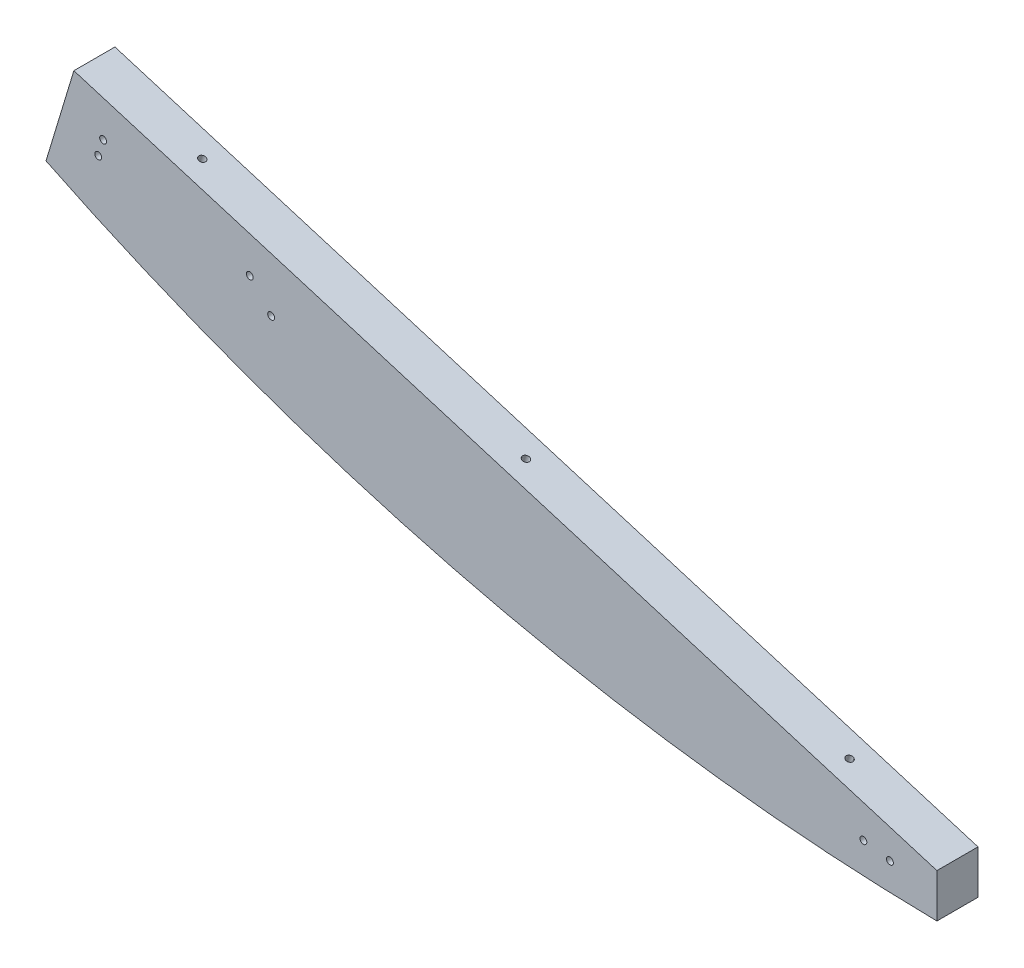
SolidWorks part; units mm, degrees
material "Beech"
ref_plane "Front Plane" through (0, 0, 0) normal (0, 0, 1) x (1, 0, 0)
ref_plane "Top Plane" through (0, 0, 0) normal (0, 1, 0) x (1, 0, 0)
ref_plane "Right Plane" through (0, 0, 0) normal (1, 0, 0) x (0, 0, -1)
sketch "Sketch1" plane through (0, 0, 0) normal (0, 0, 1) x (1, 0, 0)
  line L0 (-400.1409, 384.3517) -> (0, 263.2469)
  line L1 (134.7, 222.4793) -> (-400.1409, 384.3517) construction
  line L2 (0, 263.2469) -> (0, 242.9943)
  line L3 (-413.0591, 341.6688) -> (-426.0964, 298.5925) construction
  line L4 (0, -223.9129) -> (0, 250.6666) construction
  line L5 (-400.1409, 384.3517) -> (-396.462, 396.5071) construction
  line L9 (-400.1409, 384.3517) -> (-413.0591, 341.6688)
  line L10 (0, 242.9943) -> (0, 198.54) construction
  arc A0 (-413.0591, 341.6688) -> (0, 242.9943) centre (13.752, 1214.4469) ccw
  arc A1 (-406.853, 338.6611) -> (0.6017, 242.9859) centre (13.752, 1214.4469) ccw construction
  arc A2 (-426.0964, 298.5925) -> (0, 198.54) centre (13.752, 1214.4469) ccw construction
  dimension "D1" = 1016
  dimension "D4" = 971.55
  dimension "D2" = 914.4
  dimension "D3" = 1214.4469
  dimension "D5" = 20.2527
extrude "Boss-Extrude1" add sketch "Sketch1" against normal blind 19.05
ref_plane "CL" through (0, 0, -9.525) normal (0, 0, 1) x (1, 0, 0)
hole_wizard "Hole1" positions "Sketch2" profile "Sketch3" legacy
sketch "Sketch2" plane through (390.3751, 158.3668, -217.3) normal (0.2897, 0.9571, 0) x (0, 0, -1)
  line L4 (-207.775, 822.0847) -> (-207.775, 404.0189) construction
  line L8 (-207.775, 822.0847) -> (-207.775, 717.5683)
  line L9 (-207.775, 717.5683) -> (-207.775, 613.0518)
  line L10 (-207.775, 613.0518) -> (-207.775, 508.5353)
  line L11 (-207.775, 508.5353) -> (-207.775, 404.0189)
  line L12 (-108.65, 822.0847) -> (-108.65, 404.0189) construction
  line L15 (0, 822.0847) -> (0, 613.0518) construction
  line L18 (-207.775, 388.2192) -> (-207.775, 263.2847) construction
  line L22 (-207.775, 388.2192) -> (-207.775, 356.9856)
  line L23 (-207.775, 356.9856) -> (-207.775, 325.752)
  line L24 (-207.775, 325.752) -> (-207.775, 294.5183)
  line L25 (-207.775, 294.5183) -> (-207.775, 263.2847)
  line L26 (0, 388.2192) -> (0, 263.2847) construction
  line L30 (0, 263.2847) -> (0, 294.5183)
  line L31 (0, 294.5183) -> (0, 325.752)
  line L32 (0, 325.752) -> (0, 356.9856)
  line L33 (0, 356.9856) -> (0, 388.2192)
  point P24 (-207.775, 613.0518)
  point P31 (-207.775, 456.2771)
  point P33 (-207.775, 769.8265)
  point P52 (-108.65, 456.2771)
  point P54 (-108.65, 630.1265)
  point P56 (-108.65, 769.8265)
  point P76 (-207.775, 356.9856)
  point P80 (-207.775, 294.5183)
  point P99 (0, 294.5183)
  point P104 (0, 356.9856)
  point P113 (207.775, 294.5183)
  point P114 (207.775, 356.9856)
  point P115 (108.65, 769.8265)
  point P116 (108.65, 630.1265)
  point P117 (108.65, 456.2771)
  point P118 (207.775, 769.8265)
  point P119 (207.775, 456.2771)
  point P120 (207.775, 613.0518)
  dimension "D1" = 139.7
sketch "Sketch3" plane through (-196.3915, 335.9548, -425.075) normal (0, 0, 1) x (-0.9571, 0.2897, 0)
  line L0 (0, 0) -> (0, 32.7039)
  line L1 (0, 32.7039) -> (1.5875, 31.75)
  line L2 (1.5875, 31.75) -> (1.5875, 4.0177)
  line L3 (1.5875, 4.0177) -> (5.08, 0)
  line L4 (5.08, 0) -> (0, 0)
  line L5 (0, -14.3089) -> (0, 102.4216) construction
  line L6 (0, 32.7039) -> (-1.5875, 31.75) construction
  line L7 (-1.5875, 4.0177) -> (-5.08, 0) construction
  dimension "Diameter" = 3.175
  dimension "Depth" = 31.75
  dimension "C-Sink Diameter" = 10.16
  dimension "C-Sink Angle" = 82
  dimension "Drill Angle" = 118
hole_wizard "Hole2" positions "Sketch4" profile "Sketch5" legacy
sketch "Sketch4" plane through (277.2867, -215.2871, 12.7) normal (0, 0, 1) x (-0.09, 0.9959, 0)
  line L0 (54.6742, 260.7254) -> (44.8416, 151.8686) construction
  line L6 (458.2175, 188.8136) -> (426.7882, 117.3689) construction
  line L11 (486.0396, 272.5028) -> (513.4071, 262.4897) construction
  line L19 (643.2075, 626.7743) -> (602.3132, 525.5573) construction
  line L24 (664.0363, 618.3589) -> (454.7061, 100.2486) construction
  line L28 (664.0363, 618.3589) -> (611.7037, 488.8313)
  line L29 (611.7037, 488.8313) -> (559.3712, 359.3037)
  line L30 (559.3712, 359.3037) -> (507.0387, 229.7761)
  line L31 (507.0387, 229.7761) -> (454.7061, 100.2486)
  line L33 (513.4071, 262.4897) -> (486.0396, 272.5028)
  point P12 (52.9605, 241.7526)
  point P14 (47.6978, 183.4898)
  point P29 (434.4591, 134.8062)
  point P31 (453.1036, 177.1887)
  point P48 (499.7233, 267.4963)
  point P79 (636.0712, 609.1114)
  point P81 (609.4494, 543.2202)
  point P98 (559.3712, 359.3037)
  point P100 (507.0387, 229.7761)
  point P112 (637.87, 553.5951)
  dimension "D1" = 19.05
  dimension "D2" = 31.75
  dimension "D3" = 12.7
  dimension "D4" = 19.05
  dimension "D5" = 19.05
  dimension "D6" = 19.05
sketch "Sketch5" plane through (-331.4463, 370.1954, 12.7) normal (1, 0, 0) x (0, -1, 0)
  line L0 (0, 0) -> (0, 32.7039)
  line L1 (0, 32.7039) -> (1.5875, 31.75)
  line L2 (1.5875, 31.75) -> (1.5875, 4.0177)
  line L3 (1.5875, 4.0177) -> (5.08, 0)
  line L4 (5.08, 0) -> (0, 0)
  line L5 (0, -14.3089) -> (0, 102.4216) construction
  line L6 (0, 32.7039) -> (-1.5875, 31.75) construction
  line L7 (-1.5875, 4.0177) -> (-5.08, 0) construction
  dimension "Diameter" = 3.175
  dimension "Depth" = 31.75
  dimension "C-Sink Diameter" = 10.16
  dimension "C-Sink Angle" = 82
  dimension "Drill Angle" = 118
hole_wizard "Hole3" positions "Sketch6" profile "Sketch7" legacy
sketch "Sketch6" plane through (277.2867, -215.2871, -31.75) normal (0, 0, -1) x (0.09, -0.9959, 0)
  point P4 (-507.0387, 229.7761)
  point P6 (-559.3712, 359.3037)
  point P8 (-637.87, 553.5951)
  point P10 (-628.7751, 612.0592)
  point P12 (-597.3958, 534.3927)
  point P16 (-496.527, 255.4282)
  point P18 (-441.05, 168.3613)
  point P20 (-426.601, 135.516)
  point P22 (-41.7953, 242.7611)
  point P24 (-36.5327, 184.4983)
sketch "Sketch7" plane through (2.8292, 269.0251, -31.75) normal (1, 0, 0) x (0, 1, 0)
  line L0 (0, 0) -> (0, 32.7039)
  line L1 (0, 32.7039) -> (1.5875, 31.75)
  line L2 (1.5875, 31.75) -> (1.5875, 4.0177)
  line L3 (1.5875, 4.0177) -> (5.08, 0)
  line L4 (5.08, 0) -> (0, 0)
  line L5 (0, -14.3089) -> (0, 102.4216) construction
  line L6 (0, 32.7039) -> (-1.5875, 31.75) construction
  line L7 (-1.5875, 4.0177) -> (-5.08, 0) construction
  dimension "Diameter" = 3.175
  dimension "Depth" = 31.75
  dimension "C-Sink Diameter" = 10.16
  dimension "C-Sink Angle" = 82
  dimension "Drill Angle" = 118
hole_wizard "Hole4" positions "Sketch8" profile "Sketch9" legacy
sketch "Sketch8" plane through (-521.7058, 26.5321, -217.3) normal (-0.9571, 0.2897, 0) x (0, 0, 1)
  line L0 (207.775, 377.6924) -> (207.775, 333.0975) construction
  line L4 (108.65, 377.6924) -> (108.65, 333.0975) construction
  line L8 (175, 506.2803) -> (175, 390.3924) construction
  line L12 (94.25, 390.3924) -> (94.25, 377.6924) construction
  line L17 (94.25, 384.0424) -> (217.3, 384.0424) construction
  line L19 (94.25, 384.0424) -> (135.2667, 384.0424)
  line L20 (135.2667, 384.0424) -> (176.2833, 384.0424)
  line L21 (176.2833, 384.0424) -> (217.3, 384.0424)
  line L22 (0, 333.0975) -> (0, 390.3924) construction
  point P39 (108.65, 355.3949)
  point P41 (207.775, 355.3949)
  point P43 (175, 448.3363)
  point P47 (135.2667, 384.0424)
  point P49 (176.2833, 384.0424)
  point P65 (-175, 448.3363)
  point P66 (-135.2667, 384.0424)
  point P67 (-176.2833, 384.0424)
  point P68 (-207.775, 355.3949)
  point P69 (-108.65, 355.3949)
sketch "Sketch9" plane through (-418.7555, 366.6892, -325.95) normal (0, 0, 1) x (-0.2897, -0.9571, 0)
  line L0 (0, 0) -> (0, 39.0539)
  line L1 (0, 39.0539) -> (1.5875, 38.1)
  line L2 (1.5875, 38.1) -> (1.5875, 4.0177)
  line L3 (1.5875, 4.0177) -> (5.08, 0)
  line L4 (5.08, 0) -> (0, 0)
  line L5 (0, -14.3089) -> (0, 102.4216) construction
  line L6 (0, 39.0539) -> (-1.5875, 38.1) construction
  line L7 (-1.5875, 4.0177) -> (-5.08, 0) construction
  dimension "Diameter" = 3.175
  dimension "Depth" = 38.1
  dimension "C-Sink Diameter" = 10.16
  dimension "C-Sink Angle" = 82
  dimension "Drill Angle" = 118
hole_wizard "Hole5" positions "Sketch10" profile "Sketch11" legacy
sketch "Sketch10" plane through (-521.7058, 26.5321, -118.175) normal (-0.9571, 0.2897, 0) x (0, 0, 1)
  line L0 (207.775, 377.6924) -> (207.775, 288.0915) construction
  line L4 (108.65, 377.6924) -> (108.65, 288.0915) construction
  line L8 (175, 506.2803) -> (175, 390.3924) construction
  line L12 (94.25, 390.3924) -> (94.25, 377.6924) construction
  line L17 (94.25, 384.0424) -> (217.3, 384.0424) construction
  line L19 (94.25, 384.0424) -> (135.2667, 384.0424)
  line L20 (135.2667, 384.0424) -> (176.2833, 384.0424)
  line L21 (176.2833, 384.0424) -> (217.3, 384.0424)
  line L22 (0, 288.0915) -> (0, 390.3924) construction
  point P39 (108.65, 332.8919)
  point P41 (207.775, 332.8919)
  point P43 (175, 448.3363)
  point P47 (135.2667, 384.0424)
  point P49 (176.2833, 384.0424)
  point P65 (-175, 448.3363)
  point P66 (-135.2667, 384.0424)
  point P67 (-176.2833, 384.0424)
  point P68 (-207.775, 332.8919)
  point P69 (-108.65, 332.8919)
sketch "Sketch11" plane through (-425.2741, 345.151, -226.825) normal (0, 0, 1) x (-0.2897, -0.9571, 0)
  line L0 (0, 0) -> (0, 39.0539)
  line L1 (0, 39.0539) -> (1.5875, 38.1)
  line L2 (1.5875, 38.1) -> (1.5875, 4.0177)
  line L3 (1.5875, 4.0177) -> (5.08, 0)
  line L4 (5.08, 0) -> (0, 0)
  line L5 (0, -14.3089) -> (0, 102.4216) construction
  line L6 (0, 39.0539) -> (-1.5875, 38.1) construction
  line L7 (-1.5875, 4.0177) -> (-5.08, 0) construction
  dimension "Diameter" = 3.175
  dimension "Depth" = 38.1
  dimension "C-Sink Diameter" = 10.16
  dimension "C-Sink Angle" = 82
  dimension "Drill Angle" = 118
hole_wizard "Hole6" positions "Sketch12" profile "Sketch13" legacy
sketch "Sketch12" plane through (-521.7058, 26.5321, 99.125) normal (-0.9571, 0.2897, 0) x (0, 0, 1)
  line L0 (207.775, 377.6924) -> (207.775, 288.0915) construction
  line L4 (108.65, 377.6924) -> (108.65, 288.0915) construction
  line L8 (175, 506.2803) -> (175, 390.3924) construction
  line L12 (94.25, 390.3924) -> (94.25, 377.6924) construction
  line L17 (94.25, 384.0424) -> (217.3, 384.0424) construction
  line L19 (94.25, 384.0424) -> (135.2667, 384.0424)
  line L20 (135.2667, 384.0424) -> (176.2833, 384.0424)
  line L21 (176.2833, 384.0424) -> (217.3, 384.0424)
  line L22 (0, 288.0915) -> (0, 390.3924) construction
  point P39 (108.65, 332.8919)
  point P41 (207.775, 332.8919)
  point P43 (175, 448.3363)
  point P47 (135.2667, 384.0424)
  point P49 (176.2833, 384.0424)
  point P65 (-175, 448.3363)
  point P66 (-135.2667, 384.0424)
  point P67 (-176.2833, 384.0424)
  point P68 (-207.775, 332.8919)
  point P69 (-108.65, 332.8919)
sketch "Sketch13" plane through (-425.2741, 345.151, -9.525) normal (0, 0, 1) x (-0.2897, -0.9571, 0)
  line L0 (0, 0) -> (0, 39.0539)
  line L1 (0, 39.0539) -> (1.5875, 38.1)
  line L2 (1.5875, 38.1) -> (1.5875, 4.0177)
  line L3 (1.5875, 4.0177) -> (5.08, 0)
  line L4 (5.08, 0) -> (0, 0)
  line L5 (0, -14.3089) -> (0, 102.4216) construction
  line L6 (0, 39.0539) -> (-1.5875, 38.1) construction
  line L7 (-1.5875, 4.0177) -> (-5.08, 0) construction
  dimension "Diameter" = 3.175
  dimension "Depth" = 38.1
  dimension "C-Sink Diameter" = 10.16
  dimension "C-Sink Angle" = 82
  dimension "Drill Angle" = 118
hole_wizard "Hole7" positions "Sketch14" profile "Sketch15" legacy
sketch "Sketch14" plane through (-521.7058, 26.5321, 198.25) normal (-0.9571, 0.2897, 0) x (0, 0, 1)
  line L0 (207.775, 377.6924) -> (207.775, 333.0975) construction
  line L4 (108.65, 377.6924) -> (108.65, 333.0975) construction
  line L8 (175, 506.2803) -> (175, 390.3924) construction
  line L12 (94.25, 390.3924) -> (94.25, 377.6924) construction
  line L17 (94.25, 384.0424) -> (217.3, 384.0424) construction
  line L19 (94.25, 384.0424) -> (135.2667, 384.0424)
  line L20 (135.2667, 384.0424) -> (176.2833, 384.0424)
  line L21 (176.2833, 384.0424) -> (217.3, 384.0424)
  line L22 (0, 333.0975) -> (0, 390.3924) construction
  point P39 (108.65, 355.3949)
  point P41 (207.775, 355.3949)
  point P43 (175, 448.3363)
  point P47 (135.2667, 384.0424)
  point P49 (176.2833, 384.0424)
  point P65 (-175, 448.3363)
  point P66 (-135.2667, 384.0424)
  point P67 (-176.2833, 384.0424)
  point P68 (-207.775, 355.3949)
  point P69 (-108.65, 355.3949)
sketch "Sketch15" plane through (-418.7555, 366.6892, 89.6) normal (0, 0, 1) x (-0.2897, -0.9571, 0)
  line L0 (0, 0) -> (0, 39.0539)
  line L1 (0, 39.0539) -> (1.5875, 38.1)
  line L2 (1.5875, 38.1) -> (1.5875, 4.0177)
  line L3 (1.5875, 4.0177) -> (5.08, 0)
  line L4 (5.08, 0) -> (0, 0)
  line L5 (0, -14.3089) -> (0, 102.4216) construction
  line L6 (0, 39.0539) -> (-1.5875, 38.1) construction
  line L7 (-1.5875, 4.0177) -> (-5.08, 0) construction
  dimension "Diameter" = 3.175
  dimension "Depth" = 38.1
  dimension "C-Sink Diameter" = 10.16
  dimension "C-Sink Angle" = 82
  dimension "Drill Angle" = 118
